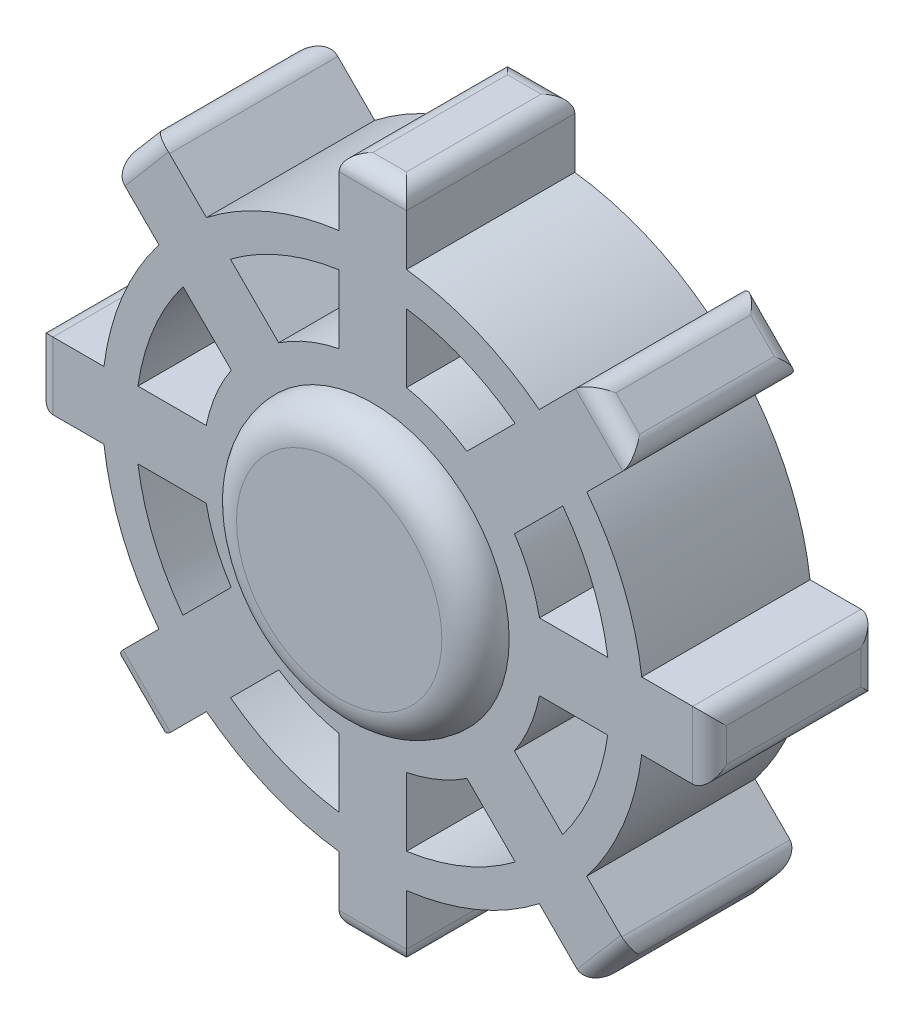
SolidWorks part; units mm, degrees
ref_plane "Front Plane" through (0, 0, 0) normal (0, 0, 1) x (1, 0, 0)
ref_plane "Top Plane" through (0, 0, 0) normal (0, 1, 0) x (1, 0, 0)
ref_plane "Right Plane" through (0, 0, 0) normal (1, 0, 0) x (0, 0, -1)
sketch "Sketch1" plane through (0, 0, 0) normal (0, 0, 1) x (1, 0, 0)
  line L1 (1, -10) -> (-1, -10)
  line L2 (1, -10) -> (1, 10)
  line L3 (1, 10) -> (-1, 10)
  line L4 (-1, -10) -> (-1, 10)
  line L5 (1, -10) -> (-1, 10) construction
  line L6 (1, 10) -> (-1, -10) construction
  line L7 (-10, -1) -> (10, -1)
  line L8 (-10, -1) -> (-10, 1)
  line L9 (-10, 1) -> (10, 1)
  line L10 (10, -1) -> (10, 1)
  line L11 (-10, -1) -> (10, 1) construction
  line L12 (-10, 1) -> (10, -1) construction
  line L13 (-7.7747, -6.3605) -> (-6.3674, -7.7816)
  line L14 (-7.7747, -6.3605) -> (6.3674, 7.7816)
  line L15 (6.3674, 7.7816) -> (7.7747, 6.3605)
  line L16 (-6.3674, -7.7816) -> (7.7747, 6.3605)
  line L17 (-7.7747, -6.3605) -> (7.7747, 6.3605) construction
  line L18 (6.3674, 7.7816) -> (-6.3674, -7.7816) construction
  line L22 (6.4227, -7.8324) -> (7.7194, -6.3097)
  line L23 (6.4227, -7.8324) -> (-7.7194, 6.3097)
  line L24 (-7.7194, 6.3097) -> (-6.4227, 7.8324)
  line L25 (7.7194, -6.3097) -> (-6.4227, 7.8324)
  line L26 (6.4227, -7.8324) -> (-6.4227, 7.8324) construction
  line L27 (-7.7194, 6.3097) -> (7.7194, -6.3097) construction
  line L29 (0.35, -3.05) -> (-0.35, -3.05)
  line L30 (0.35, -3.05) -> (0.35, 3.05)
  line L31 (0.35, 3.05) -> (-0.35, 3.05)
  line L32 (-0.35, -3.05) -> (-0.35, 3.05)
  line L33 (0.35, -3.05) -> (-0.35, 3.05) construction
  line L34 (0.35, 3.05) -> (-0.35, -3.05) construction
  circle A0 centre (0, 0) radius 3.05
  circle A1 centre (0, 0) radius 5.05
  point P20 (0, 0)
  dimension "D1" = 6.1
  dimension "D2" = 2
  dimension "D3" = 45
  dimension "D4" = 2
  dimension "D5" = 135
  dimension "D6" = 20
  dimension "D7" = 0.7
extrude "Boss-Extrude1" add sketch "Sketch1" along normal blind 5 contours A1 L2 L3 L4 | A1 L25 L24 L23 | A1 L16 L15 L14 | A1 L7 L10 L9 | A1 L23 L22 L25 | A1 L4 L1 L2 | A1 L14 L13 L16 | L16 A1 L14 A0 | L14 A1 L2 A0 | L2 A1 L4 A0 | L4 A1 L25 A0 | L25 A1 L23 A0 | L23 A1 L9 A0 | L9 A1 L7 A0 | L7 A1 L14 A0 | L14 A1 L16 A0 | L16 A1 L4 A0 | L2 A1 L23 A0 | L4 A1 L2 A0 | L25 A1 L7 A0 | L23 A1 L25 A0 | L7 A1 L9 A0 | L9 A1 L16 A0 | A1 L9 L8 L7 | L30 A0 L32 L25 L14 | L32 L14 L25 | L25 L30 L14 | L32 L9 L30 L25 L14 | L32 L7 L30 L9 | L32 A0 L30 L23 L16 | L32 L16 L23 | L23 L30 L16 | L32 L23 L16 L30 L7 region at (0, -7.5083, 0) region at (0, -4.0063, 0) region at (1.6319, -3.9354, 0) region at (-1.6307, -3.9367, 0) region at (5.3056, -5.3132, 0) region at (2.8323, -2.8323, 0) region at (-2.8321, -2.8321, 0) region at (-5.3089, -5.3094, 0) region at (0.0003, -2.3116, 0) region at (3.9354, -1.6319, 0) region at (-3.9367, -1.6307, 0) region at (0.2341, -1.4119, 0) region at (7.5083, 0, 0) region at (4.0052, 0, 0) region at (-0.2326, -1.4119, 0) region at (-4.0052, 0, 0) region at (-7.5083, 0, 0) region at (0.0017, -1.14, 0) region at (-3.9354, 1.6319, 0) region at (0, 0, 0) region at (3.9367, 1.6307, 0) region at (-2.8323, 2.8323, 0) region at (-5.3056, 5.3132, 0) region at (-0.0017, 1.14, 0) region at (5.3089, 5.3094, 0) region at (2.8321, 2.8321, 0) region at (-1.6319, 3.9354, 0) region at (0.2326, 1.4119, 0) region at (1.6307, 3.9367, 0) region at (-0.2341, 1.4119, 0) region at (0, 4.0063, 0) region at (0, 7.5083, 0) region at (-0.0003, 2.3116, 0)
fillet "Fillet1" radius 0.5 32 edges at (6.4227, -7.8324, 2.5) (7.0711, -7.0711, 5) (7.7194, -6.3097, 2.5) (7.0711, -7.0711, 0) (10, -1, 2.5) (10, 0, 5) (10, 1, 2.5) (10, 0, 0) (7.7747, 6.3605, 2.5) (7.0711, 7.0711, 5) (6.3674, 7.7816, 2.5) (7.0711, 7.0711, 0) (-6.4227, 7.8324, 2.5) (-7.0711, 7.0711, 5) (-7.7194, 6.3097, 2.5) (-7.0711, 7.0711, 0) (-1, -10, 2.5) (0, -10, 5) (1, -10, 2.5) (0, -10, 0) (-7.7747, -6.3605, 2.5) (-7.0711, -7.0711, 5) (-6.3674, -7.7816, 2.5) (-7.0711, -7.0711, 0) (-10, 1, 2.5) (-10, 0, 5) (-10, -1, 2.5) (-10, 0, 0) (1, 10, 2.5) (0, 10, 5) (-1, 10, 2.5) (0, 10, 0)
sketch "Sketch2" plane through (0, 0, 5) normal (0, 0, 1) x (1, 0, 0)
  circle A0 centre (0, 0) radius 7.05
  circle A1 centre (0, 0) radius 8.05
  arc A2 (-1, 4.95) -> (-2.7958, 4.2055) centre (0, 0) ccw construction
  dimension "D1" = 1
  dimension "D2" = 2
extrude "Boss-Extrude2" add sketch "Sketch2" against normal up to surface (5 mm away) up to face at (0, 0, 0)
sketch "Sketch6" plane through (0, 0, 5) normal (0, 0, 1) x (1, 0, 0)
  circle A0 centre (0, 0) radius 4.05
  arc A1 (-0.35, 3.0299) -> (-0.35, -3.0299) centre (0, 0) ccw construction
  arc A2 (-4.2055, 2.7958) -> (-4.95, 1) centre (0, 0) ccw construction
  dimension "D1" = 1
extrude "Boss-Extrude8" add sketch "Sketch6" along normal blind 1 contours A0
fillet "Fillet2" radius 1 1 edges at (4.05, 0, 6)
